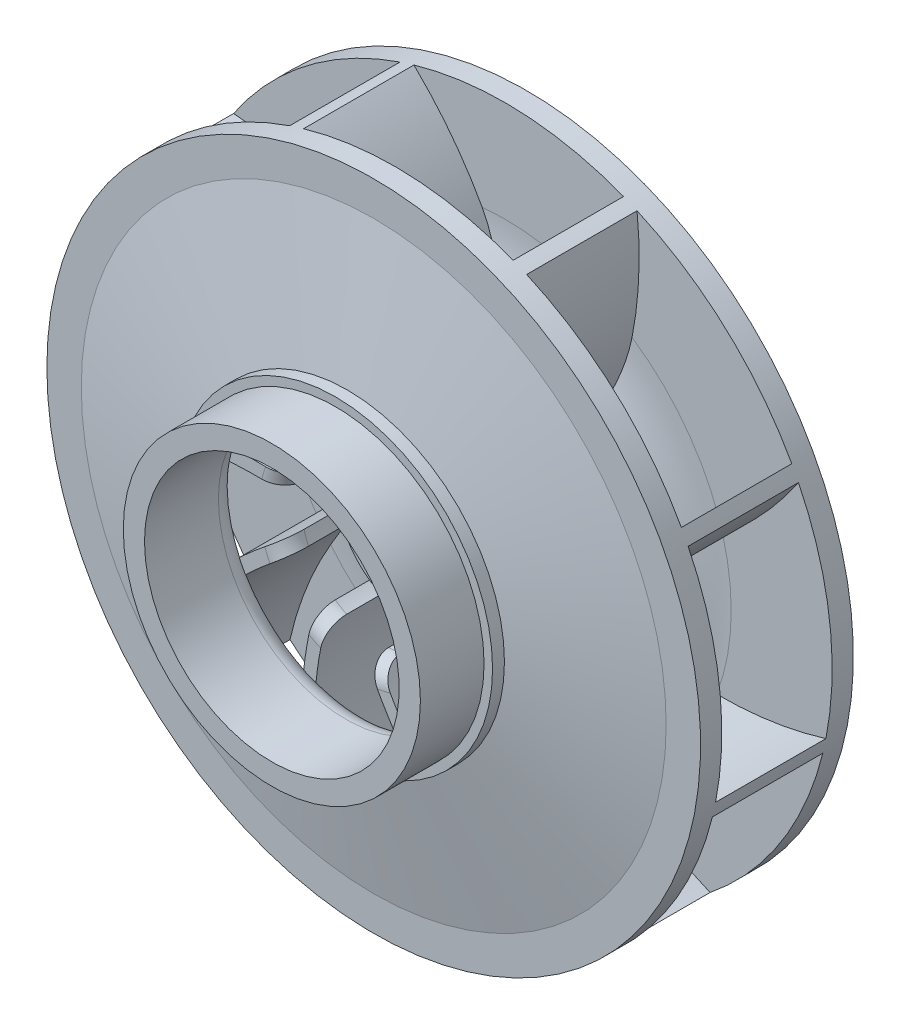
SolidWorks part; units mm, degrees
material "Nickel"
ref_plane "Front Plane" through (0, 0, 0) normal (0, 0, 1) x (1, 0, 0)
ref_plane "Top Plane" through (0, 0, 0) normal (0, 1, 0) x (1, 0, 0)
ref_plane "Right Plane" through (0, 0, 0) normal (1, 0, 0) x (0, 0, -1)
sketch "Sketch1" plane through (0, 0, 0) normal (1, 0, 0) x (0, 0, -1)
  line L0 (0, 0) -> (-74.4601, 0) construction
  line L1 (-14.3699, 42.5) -> (-14.3699, 37.5)
  line L2 (-14.3699, 37.5) -> (-29.3699, 37.5)
  line L3 (-14.3699, 42.5) -> (-34.3699, 42.5)
  line L4 (-29.3699, 37.5) -> (-29.3699, 36)
  line L5 (-29.3699, 36) -> (-34.3699, 36)
  line L6 (-34.3699, 36) -> (-34.3699, 22)
  line L7 (-34.3699, 22) -> (-27.2771, 22)
  line L8 (-27.2771, 22) -> (-27.2771, 9)
  line L9 (-27.2771, 9) -> (-61.3699, 9)
  line L10 (-61.3699, 9) -> (-61.3699, 17.5)
  line L11 (-34.3699, 42.5) -> (-34.3699, 77)
  line L12 (-34.3699, 77) -> (-39.3699, 77)
  line L13 (-39.3699, 77) -> (-39.3699, 53.2211)
  line L14 (-65.3699, 77) -> (-70.3699, 77)
  line L15 (-70.3699, 77) -> (-70.3699, 68.8962)
  line L16 (-70.3699, 68.8962) -> (-76.5699, 37)
  line L17 (-76.5699, 37) -> (-79.3699, 37)
  line L18 (-79.3699, 37) -> (-79.3699, 35)
  line L19 (-79.3699, 35) -> (-94.3699, 35)
  line L20 (-94.3699, 35) -> (-94.3699, 30)
  line L21 (-94.3699, 30) -> (-76.9586, 30)
  line L22 (-65.3699, 77) -> (-65.3699, 68.4148)
  line L23 (-65.3699, 68.4148) -> (-72.0505, 34.046)
  arc A0 (-39.3699, 53.2211) -> (-61.3699, 17.5) centre (-79.3699, 53.2211) cw
  arc A1 (-76.9586, 30) -> (-72.0505, 34.046) centre (-76.9586, 35) ccw
  dimension "D11" = 40
  dimension "D24" = 5
  dimension "D1" = 85
  dimension "D2" = 75
  dimension "D3" = 72
  dimension "D4" = 44
  dimension "D5" = 18
  dimension "D6" = 47
  dimension "D7" = 20
  dimension "D8" = 15
  dimension "D9" = 5
  dimension "D10" = 154
  dimension "D12" = 35
  dimension "D13" = 20
  dimension "D14" = 5
  dimension "D15" = 26
  dimension "D16" = 17.8
  dimension "D17" = 15
  dimension "D18" = 70
  dimension "D19" = 60
  dimension "D20" = 74
  dimension "D21" = 5
  dimension "D22" = 11
  dimension "D23" = 80
revolve "Revolve1" add sketch "Sketch1" angle 360 about L0
sketch "Sketch2" plane through (0, 0, 27.2771) normal (0, 0, -1) x (-1, 0, 0)
  line L1 (-3, 4.999) -> (3, 4.999)
  line L2 (-3, 4.999) -> (-3, 11.8)
  line L3 (-3, 11.8) -> (3, 11.8)
  line L4 (3, 4.999) -> (3, 11.8)
  line L5 (-3, 4.999) -> (3, 11.8) construction
  line L6 (-3, 11.8) -> (3, 4.999) construction
  point P0 (0, 8.3995)
  point P5 (0, 0)
  dimension "D1" = 6
  dimension "D2" = 11.8
extrude "Cut-Extrude1" cut sketch "Sketch2" against normal up to next
ref_plane "Plane1" through (0, 0, 61.3699) normal (0, 0, -1) x (-1, 0, 0)
sketch "Sketch3" plane through (0, 0, 61.3699) normal (0, 0, -1) x (-1, 0, 0)
  arc A0 (10.5808, 15.7812) -> (7.8513, 17.302) centre (0, 0) ccw
  arc A3 (65.8565, 39.8989) -> (64.0117, 42.796) centre (0, 0) ccw
  arc A4 (64.0117, 42.796) -> (7.8513, 17.302) centre (70, -45) ccw
  arc A5 (65.8565, 39.8989) -> (10.5808, 15.7812) centre (70, -45) ccw
  dimension "D1" = 38
  dimension "D2" = 45
  dimension "D3" = 70
extrude "Boss-Extrude1" add sketch "Sketch3" along normal up to next and the other way blind 12
fillet "Fillet1" radius 5 1 edges at (-9.2473, 16.5978, 73.3699)
pattern_circular "CirPattern1" count 9 over 360 about axis through (0, 0, 0) along (0, 0, -1) of "Boss-Extrude1", "Fillet1"
sketch "Sketch5" plane through (0, 0, 0) normal (1, 0, 0) x (0, 0, -1)
  line L0 (0, 0) -> (-113.2589, 0) construction
  line L1 (-70.3699, 77) -> (-70.3699, 68.8962)
  line L2 (-70.3699, 68.8962) -> (-76.5699, 37)
  line L3 (-76.5699, 37) -> (-76.5699, 77)
  line L4 (-76.5699, 77) -> (-70.3699, 77)
revolve "Cut-Revolve2" cut sketch "Sketch5" angle 360 about L0
chamfer "Chamfer1" distance 1 angle 45 1 edges at (-42.5, 0, 14.3699)
